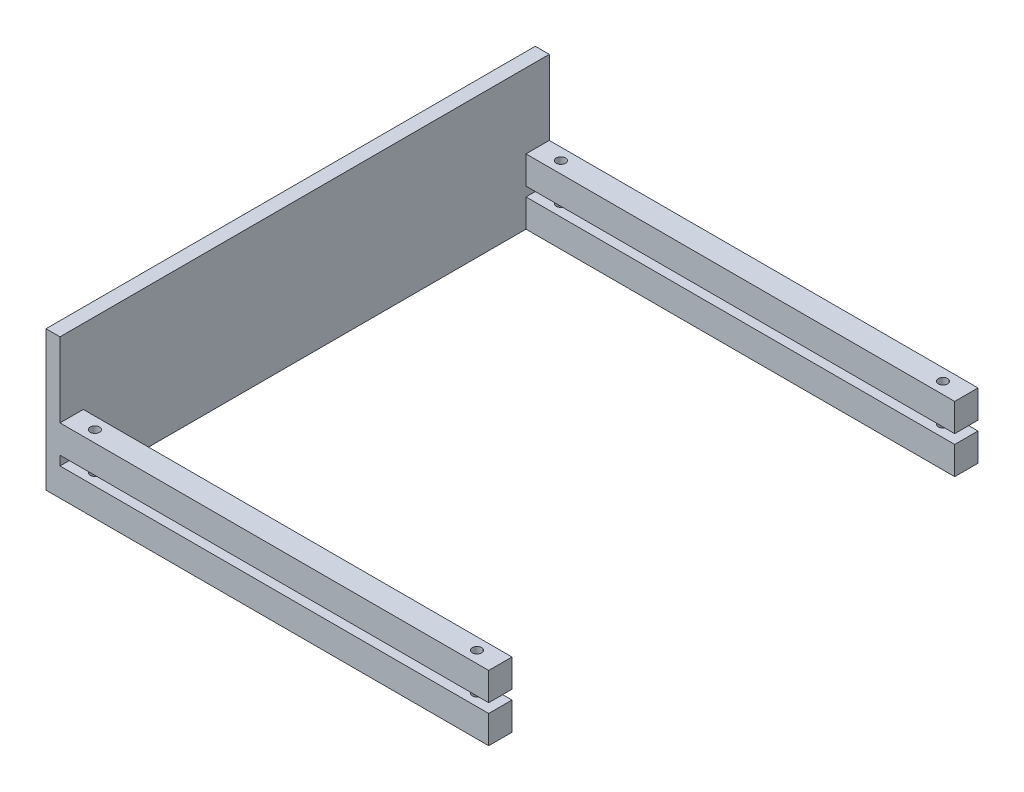
SolidWorks part; units mm, degrees
ref_plane "Front Plane" through (0, 0, 0) normal (0, 0, 1) x (1, 0, 0)
ref_plane "Top Plane" through (0, 0, 0) normal (0, 1, 0) x (1, 0, 0)
ref_plane "Right Plane" through (0, 0, 0) normal (1, 0, 0) x (0, 0, -1)
sketch "Sketch1" plane through (0, 0, 0) normal (0, 0, 1) x (1, 0, 0)
  line L0 (0, 16) -> (0, 0)
  line L1 (0, 16) -> (-3, 16)
  line L2 (-3, 16) -> (-3, -14)
  line L3 (-3, -14) -> (92, -14)
  line L4 (92, -14) -> (92, 0)
  line L5 (92, 0) -> (0, 0)
  dimension "D1" = 95
  dimension "D2" = 14
  dimension "D3" = 3
  dimension "D4" = 30
extrude "Boss-Extrude1" add sketch "Sketch1" against normal blind 105
sketch "Sketch2" plane through (0, 0, 0) normal (1, 0, 0) x (0, 0, -1)
  line L10 (0, -6) -> (5, -6)
  line L11 (0, -14) -> (0, 0) construction
  line L12 (5, -6) -> (5, 0)
  line L13 (105, 0) -> (0, 0) construction
  line L14 (5, 0) -> (100, 0)
  line L25 (100, 0) -> (100, -6)
  line L27 (100, -6) -> (105, -6)
  line L28 (105, -14) -> (105, 0) construction
  line L29 (105, -6) -> (105, -8)
  line L30 (105, -8) -> (100, -8)
  line L31 (100, -8) -> (100, -14)
  line L32 (105, -14) -> (0, -14) construction
  line L33 (100, -14) -> (5, -14)
  line L34 (5, -14) -> (5, -8)
  line L35 (5, -8) -> (0, -8)
  line L36 (0, -8) -> (0, -6)
  dimension "D1" = 6
  dimension "D2" = 6
  dimension "D3" = 5
  dimension "D4" = 5
extrude "Cut-Extrude1" cut sketch "Sketch2" along normal through all contours L12 L14 L25 L27 L29 L30 L31 L33 L34 L35 L36 L10
sketch "Sketch3" plane through (0, 0, 0) normal (0, 1, 0) x (1, 0, 0)
  line L0 (92, 105) -> (92, 100) construction
  line L1 (92, 5) -> (92, 0) construction
  line L2 (0, 5) -> (0, 0) construction
  circle A0 centre (87, 102.5) radius 1
  circle A1 centre (5, 102.5) radius 1
  circle A2 centre (5, 2.5) radius 1
  circle A3 centre (87, 2.5) radius 1
  point P8 (0, 0)
  point P9 (0, 0)
  point P10 (0, 0)
  point P11 (0, 0)
  point P12 (93.4346, 97.1379)
  point P13 (83.0034, 94.3767)
  point P14 (87.526, 102.5579)
  point P17 (92, 102.5)
  point P18 (85.9067, 2.065)
  point P21 (92, 2.5)
  dimension "D1" = 2
  dimension "D2" = 5
  dimension "D3" = 5
extrude "Cut-Extrude2" cut sketch "Sketch3" against normal through all
